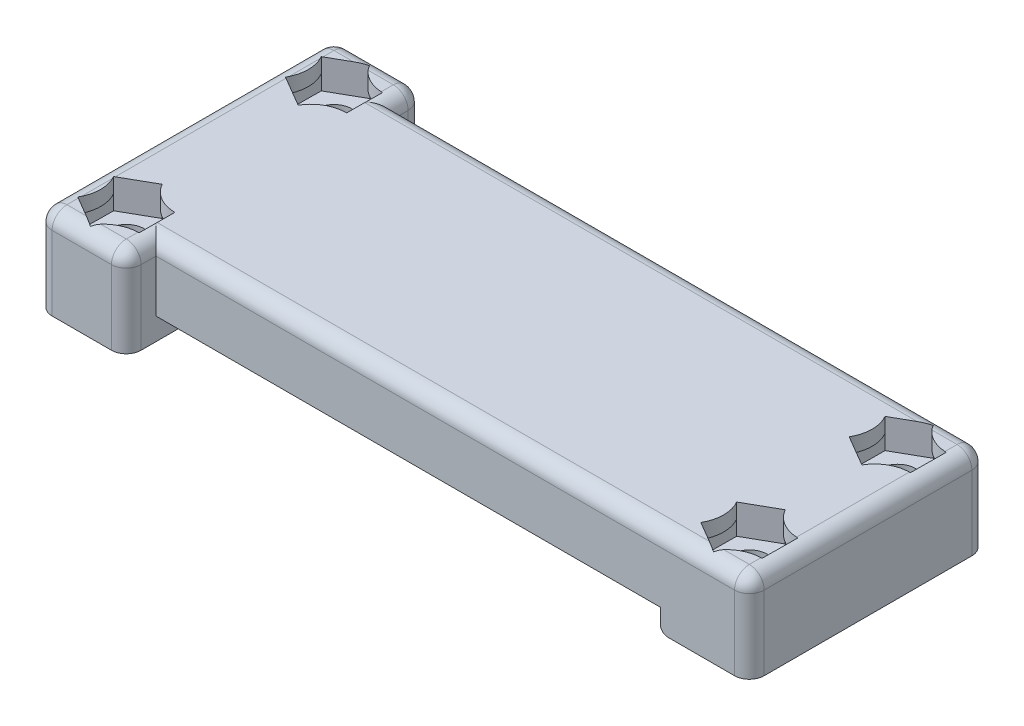
SolidWorks part; units mm, degrees
material "ABS PC"
ref_plane "前基準面" through (0, 0, 0) normal (0, 0, 1) x (1, 0, 0)
ref_plane "上基準面" through (0, 0, 0) normal (0, 1, 0) x (1, 0, 0)
ref_plane "右基準面" through (0, 0, 0) normal (1, 0, 0) x (0, 0, -1)
sketch "草圖1" plane through (0, 0, 0) normal (0, 1, 0) x (1, 0, 0)
  line L0 (0, 0) -> (-20, 0) construction
  line L1 (-20, -8) -> (20, -8)
  line L2 (-20, -4) -> (-20, 4)
  line L3 (-20, 8) -> (20, 8)
  line L4 (20, -8) -> (20, 8)
  line L5 (-20, 4) -> (-26, 4)
  line L6 (-26, 4) -> (-26, 10)
  line L7 (-26, 10) -> (-20, 10)
  line L8 (-20, 10) -> (-20, 8)
  line L9 (-20, -10) -> (-20, -8)
  line L10 (-26, -10) -> (-20, -10)
  line L11 (-26, -4) -> (-26, -10)
  line L12 (-20, -4) -> (-26, -4)
  dimension "D1" = 16
  dimension "D3" = 20
  dimension "D4" = 40
extrude "填料-伸長1" add sketch "草圖1" along normal blind 6
sketch "草圖2" plane through (0, 0, 0) normal (0, 1, 0) x (1, 0, 0)
  line L1 (-26, 4) -> (-20, 4)
  line L2 (-26, 4) -> (-26, -4)
  line L3 (-26, -4) -> (-20, -4)
  line L4 (-20, 4) -> (-20, -4)
extrude "填料-伸長2" add sketch "草圖2" along normal blind 6
sketch "草圖4" plane through (0, 0, 0) normal (0, 1, 0) x (1, 0, 0)
  line L0 (-20, 0) -> (0, 0) construction
  line L1 (-26, 10) -> (-23, 10) construction
  line L2 (-26, -10) -> (-23, -10) construction
  line L3 (-26, 10) -> (-20, 10) construction
  line L4 (-23, 10) -> (-23, 7) construction
  line L5 (-23, -10) -> (-23, -7) construction
  line L6 (-25.0866, -8.1859) -> (-23.0163, -9.4)
  line L7 (-20.9297, -8.2141) -> (-20.9134, -5.8141)
  line L9 (-22.9837, -4.6) -> (-25.0703, -5.7859)
  line L10 (-22.9837, 9.4) -> (-25.0703, 8.2141)
  line L12 (-25.0866, 5.8141) -> (-23.0163, 4.6)
  line L14 (-20.9297, 5.7859) -> (-20.9134, 8.1859)
  line L21 (14.9134, 3.8141) -> (16.9837, 2.6)
  line L23 (17.0163, 7.4) -> (14.9297, 6.2141)
  line L24 (19.0703, 3.7859) -> (19.0866, 6.1859)
  line L27 (14.9134, -6.1859) -> (16.9837, -7.4)
  line L29 (17.0163, -2.6) -> (14.9297, -3.7859)
  line L30 (19.0703, -6.2141) -> (19.0866, -3.8141)
  line L31 (-25.0703, 8.2141) -> (-25.0866, 5.8141) [skipped]
  line L32 (-20.9134, 8.1859) -> (-22.9837, 9.4) [skipped]
  line L33 (-23.0163, 4.6) -> (-20.9297, 5.7859) [skipped]
  circle A0 centre (-23, -7) radius 2.0785 construction
  circle A1 centre (-23, 7) radius 2.0785 construction
  circle A2 centre (17, 5) radius 2.0785 construction
  circle A3 centre (17, -5) radius 2.0785 construction
  arc A4 (-25.0703, -5.7859) -> (-25.0866, -8.1859) centre (-27.1569, -6.9718) cw
  arc A5 (-25.0703, 8.2141) -> (-25.0866, 5.8141) centre (-27.1569, 7.0282) cw
  arc A6 (-23.0163, -9.4) -> (-20.9297, -8.2141) centre (-20.9459, -10.6141) cw
  arc A7 (-23.0163, 4.6) -> (-20.9297, 5.7859) centre (-20.9459, 3.3859) cw
  arc A8 (-22.9837, 9.4) -> (-20.9134, 8.1859) centre (-20.8972, 10.5859) ccw
  arc A9 (-22.9837, -4.6) -> (-20.9134, -5.8141) centre (-20.8972, -3.4141) ccw
  arc A10 (14.9297, 6.2141) -> (14.9134, 3.8141) centre (12.8431, 5.0282) cw
  arc A11 (16.9837, 2.6) -> (19.0703, 3.7859) centre (19.0541, 1.3859) cw
  arc A12 (17.0163, 7.4) -> (19.0866, 6.1859) centre (19.1028, 8.5859) ccw
  arc A13 (14.9297, -3.7859) -> (14.9134, -6.1859) centre (12.8431, -4.9718) cw
  arc A14 (16.9837, -7.4) -> (19.0703, -6.2141) centre (19.0541, -8.6141) cw
  arc A15 (17.0163, -2.6) -> (19.0866, -3.8141) centre (19.1028, -1.4141) ccw
  point P19 (-25.1955, 7)
  point P21 (-25.3, -7)
  point P27 (14.8045, 5)
  point P33 (14.8045, -5)
  dimension "D1" = 4.8
  dimension "D2" = 4.8
  dimension "D3" = 4.8
  dimension "D4" = 4.8
extrude "除料-伸長2" cut sketch "草圖4" along normal blind 2 from offset 4
fillet "圓角8" radius 1 2 edges at (0, 6, -8) (0, 6, 8)
fillet "圓角9" radius 1 5 edges at (20, 2.5, 8) (20, 5.7071, 7.7071) (20, 2.5, -8) (20, 5.7071, -7.7071) (20, 6, 0)
fillet "圓角10" radius 1 1 edges at (-20, 6, -8.5)
fillet "圓角11" radius 1 1 edges at (-20, 6, 8.5)
fillet "圓角12" radius 1 6 edges at (-23.5, 6, -10) (-20.2929, 5.7071, -10) (-23.5, 6, 10) (-20.2929, 5.7071, 10) (-20, 2.5, -10) (-20, 2.5, 10)
fillet "圓角13" radius 1 5 edges at (-26, 5.7071, 9.7071) (-26, 6, 0) (-26, 5.7071, -9.7071) (-26, 2.5, 10) (-26, 2.5, -10)
sketch "草圖6" plane through (0, 0, 0) normal (0, 1, 0) x (1, 0, 0)
  line L0 (-20, 8) -> (20, 8) construction
  line L1 (-20, -10) -> (-26, -10) construction
  line L2 (-20, -10) -> (-20, 10) construction
  line L3 (-20, 10) -> (-26, 10) construction
  line L4 (-26, -10) -> (-26, 10) construction
  line L5 (20, -8) -> (14, -8) construction
  line L6 (20, -8) -> (20, 8) construction
  line L7 (20, 8) -> (14, 8) construction
  line L8 (14, -8) -> (14, 8) construction
  dimension "D1" = 6
sketch "草圖8" plane through (0, 0, 0) normal (0, 1, 0) x (1, 0, 0)
  line L0 (-20, 4) -> (-20, 8)
  line L1 (-20, -8) -> (14, -8)
  line L2 (-20, -8) -> (-20, -4)
  line L3 (-20, 8) -> (14, 8)
  line L4 (14, -8) -> (14, 8)
  line L5 (-20, -4) -> (-26, -4)
  line L7 (-20, 4) -> (-26, 4)
  line L8 (-26, -4) -> (-26, 4)
extrude "除料-伸長5" cut sketch "草圖8" along normal blind 1.5
fillet "圓角14" radius 0.5 1 edges at (14, 0, 0)
sketch "草圖9" plane through (0, 0, 0) normal (0, 1, 0) x (1, 0, 0)
  line L0 (-22.9837, 9.4) -> (-23.0163, 4.6) construction
  line L1 (-22.9837, -4.6) -> (-23.0163, -9.4) construction
  line L3 (17.0163, 7.4) -> (16.9837, 2.6) construction
  line L4 (17.0163, -2.6) -> (16.9837, -7.4) construction
  circle A0 centre (-23, 7) radius 1.2
  circle A1 centre (-23, -7) radius 1.2
  circle A2 centre (17, 5) radius 1.2
  circle A3 centre (17, -5) radius 1.2
extrude "除料-伸長6" cut sketch "草圖9" along normal blind 5
fillet "圓角15" radius 0.5 4 edges at (-26, 0.75, -4) (-26, 0.75, 4) (-20, 0.75, -4) (-20, 0.75, 4)
sketch "草圖11" plane through (0, 0, 0) normal (0, 1, 0) x (1, 0, 0)
  line L0 (-22.9837, -4.6) -> (-25.0703, -5.7859)
  line L1 (-22.9837, 9.4) -> (-25.0703, 8.2141)
  line L2 (-25.0703, 8.2141) -> (-25.0866, 5.8141)
  line L3 (-25.0866, 5.8141) -> (-23.0163, 4.6)
  line L4 (-23.0163, 4.6) -> (-20.9297, 5.7859)
  line L5 (-20.9297, 5.7859) -> (-20.9134, 8.1859)
  line L6 (-20.9134, 8.1859) -> (-22.9837, 9.4)
  line L7 (-20.9297, -8.2141) -> (-20.9134, -5.8141)
  line L8 (-25.0703, -5.7859) -> (-25.0866, -8.1859)
  line L9 (-23.0163, -9.4) -> (-20.9297, -8.2141)
  line L10 (-20.9134, -5.8141) -> (-22.9837, -4.6)
  line L11 (-25.0866, -8.1859) -> (-23.0163, -9.4)
  line L12 (17.0163, 7.4) -> (14.9297, 6.2141)
  line L13 (19.0703, 3.7859) -> (19.0866, 6.1859)
  line L14 (14.9297, 6.2141) -> (14.9134, 3.8141)
  line L15 (16.9837, 2.6) -> (19.0703, 3.7859)
  line L16 (19.0866, 6.1859) -> (17.0163, 7.4)
  line L17 (14.9134, 3.8141) -> (16.9837, 2.6)
  line L18 (17.0163, -2.6) -> (14.9297, -3.7859)
  line L19 (19.0703, -6.2141) -> (19.0866, -3.8141)
  line L20 (14.9297, -3.7859) -> (14.9134, -6.1859)
  line L21 (16.9837, -7.4) -> (19.0703, -6.2141)
  line L22 (19.0866, -3.8141) -> (17.0163, -2.6)
  line L23 (14.9134, -6.1859) -> (16.9837, -7.4)
  circle A0 centre (-23, 7) radius 2.0785 construction
extrude "除料-伸長7" cut sketch "草圖11" against normal blind 1 from offset 5
